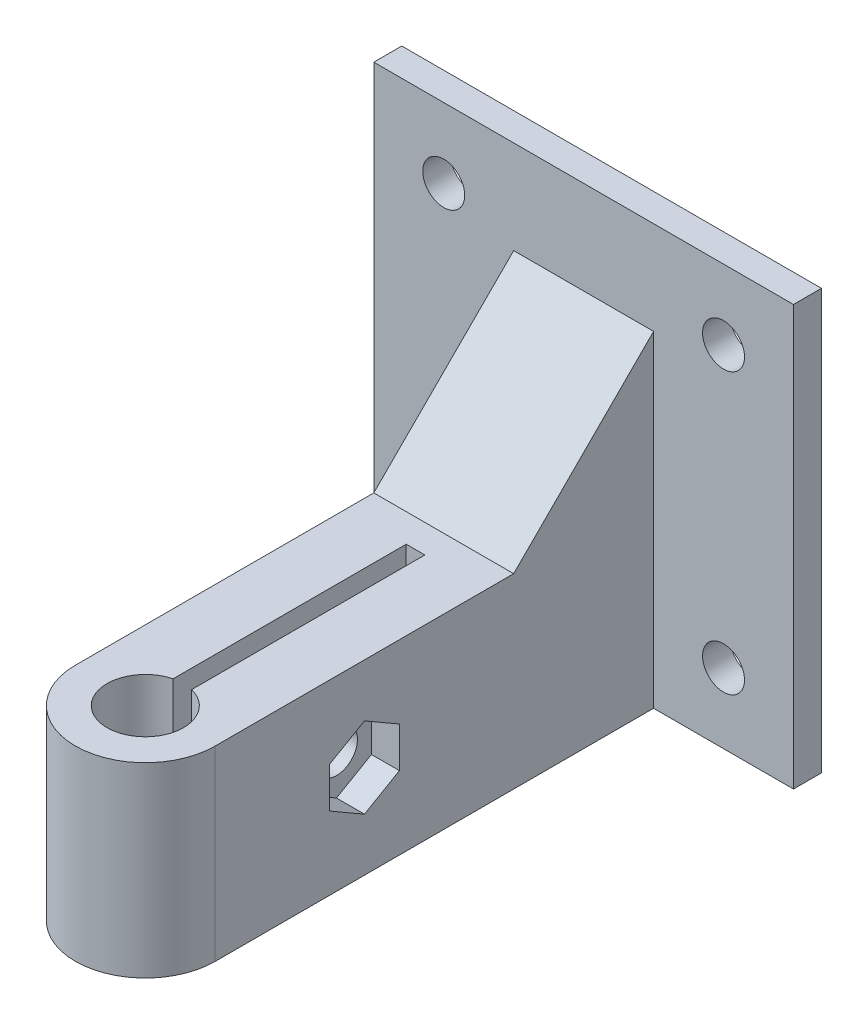
SolidWorks part; units mm, degrees
ref_plane "Front Plane" through (0, 0, 0) normal (0, 0, 1) x (1, 0, 0)
ref_plane "Top Plane" through (0, 0, 0) normal (0, 1, 0) x (1, 0, 0)
ref_plane "Right Plane" through (0, 0, 0) normal (1, 0, 0) x (0, 0, -1)
sketch "Sketch1" plane through (0, 0, 0) normal (0, 0, 1) x (1, 0, 0)
  line L0 (-15, 15) -> (-15, -15) construction
  line L1 (-22.5, -22.5) -> (22.5, -22.5)
  line L2 (-22.5, -22.5) -> (-22.5, 22.5)
  line L3 (-22.5, 22.5) -> (22.5, 22.5)
  line L4 (22.5, -22.5) -> (22.5, 22.5)
  line L5 (-22.5, -22.5) -> (22.5, 22.5) construction
  line L6 (-22.5, 22.5) -> (22.5, -22.5) construction
  circle A0 centre (-15, 15) radius 2.25
  circle A1 centre (15, 15) radius 2.25
  circle A2 centre (15, -15) radius 2.25
  circle A3 centre (-15, -15) radius 2.25
  point P0 (0, 0)
  point P14 (14.9997, -15.0003)
  dimension "D2" = 4.5
  dimension "D1" = 45
  dimension "D3" = 30
  dimension "D4" = 30
  dimension "D5" = 30
extrude "Boss-Extrude1" add sketch "Sketch1" along normal blind 3
sketch "Sketch3" plane through (0, -22.5, 0) normal (0, -1, 0) x (-1, 0, 0)
  line L0 (22.5, -3) -> (-22.5, -3) construction
  line L1 (7.5, -3) -> (-7.5, -3)
  line L2 (7.5, -3) -> (7.5, -50)
  line L3 (1, -46.0238) -> (1, -21.0238)
  line L4 (-7.5, -3) -> (-7.5, -50)
  line L6 (22.5, 0) -> (-22.5, 0) construction
  line L7 (1, -21.0238) -> (-1, -21.0238)
  line L8 (-1, -21.0238) -> (-1, -46.0238)
  line L9 (7.5, -50) -> (0, -50) construction
  arc A0 (-1, -46.0238) -> (1, -46.0238) centre (0, -50) ccw
  arc A1 (7.5, -50) -> (-7.5, -50) centre (0, -50) cw
  point P6 (0, -3)
  point P9 (0, 0)
  point P14 (0, -21.0238)
  dimension "D3" = 8.2
  dimension "D1" = 0
  dimension "D2" = 47
  dimension "D4" = 15
  dimension "D5" = 0
  dimension "D6" = 2
  dimension "D7" = 25
extrude "Boss-Extrude2" add sketch "Sketch3" against normal blind 20
chamfer "Chamfer1" distance 15 angle 45 1 edges at (0, -2.5, 3)
sketch "Sketch4" plane through (-7.5, 0, 0) normal (-1, 0, 0) x (0, 0, 1)
  line L0 (34, -2.5) -> (34, -22.5) construction
  line L1 (50, -2.5) -> (18, -2.5) construction
  line L2 (50, -22.5) -> (3, -22.5) construction
  circle A0 centre (34, -12.5) radius 2.25
  dimension "D1" = 4.5
extrude "Cut-Extrude1" cut sketch "Sketch4" against normal blind 20
sketch "Sketch5" plane through (7.5, 0, 0) normal (1, 0, 0) x (0, 0, -1)
  line L1 (-34, -16.8301) -> (-30.25, -14.6651)
  line L2 (-30.25, -14.6651) -> (-30.25, -10.3349)
  line L3 (-30.25, -10.3349) -> (-34, -8.1699)
  line L4 (-34, -8.1699) -> (-37.75, -10.3349)
  line L5 (-37.75, -10.3349) -> (-37.75, -14.6651)
  line L6 (-37.75, -14.6651) -> (-34, -16.8301)
  circle A0 centre (-34, -12.5) radius 3.75 construction
  dimension "D1" = 7.5
extrude "Cut-Extrude2" cut sketch "Sketch5" against normal blind 3
